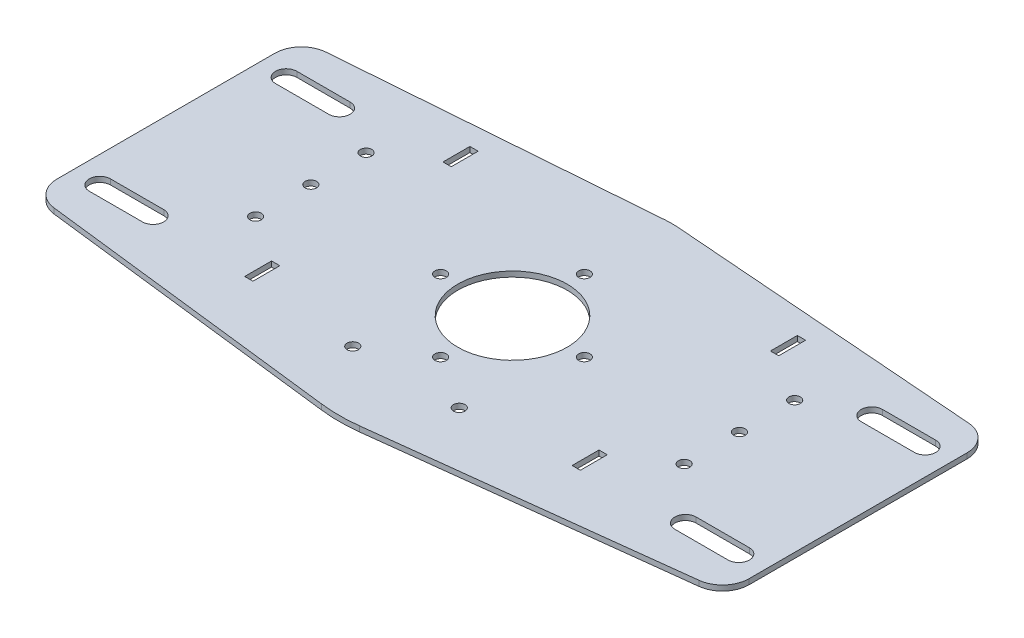
SolidWorks part; units mm, degrees
note: The reader was unsure of these and kept them because the rebuilt part matched: thickness of "Base-Flange1", "Sheet-Metal8", "Sheet-Metal9".
material "AISI 316 Stainless Steel Sheet (SS)"
ref_plane "Front Plane" through (0, 0, 0) normal (0, 0, 1) x (1, 0, 0)
ref_plane "Top Plane" through (0, 0, 0) normal (0, 1, 0) x (1, 0, 0)
ref_plane "Right Plane" through (0, 0, 0) normal (1, 0, 0) x (0, 0, -1)
sketch "Sketch1" plane through (0, 0, 0) normal (0, 1, 0) x (1, 0, 0)
  line L0 (0, -44.7868) -> (0, 44.7868) construction
  line L2 (-130, -50) -> (-130, 50)
  line L3 (-130, 50) -> (130, 50) construction
  line L4 (130, -50) -> (130, 50)
  line L5 (-44.2539, 0) -> (44.2539, 0) construction
  line L8 (-130, -50) -> (-7.0677, -64.5823)
  line L9 (130, -50) -> (7.0677, -64.5823)
  line L10 (-130, 50) -> (-2.3009, 59.823)
  line L11 (-63.05, 47.05) -> (-59.95, 47.05)
  line L12 (-63.05, 47.05) -> (-63.05, 36.95)
  line L13 (-63.05, 36.95) -> (-59.95, 36.95)
  line L14 (-59.95, 47.05) -> (-59.95, 36.95)
  line L15 (-63.05, 47.05) -> (-59.95, 36.95) construction
  line L16 (-63.05, 36.95) -> (-59.95, 47.05) construction
  line L17 (-63.05, -37.55) -> (-59.95, -37.55)
  line L18 (-63.05, -37.55) -> (-63.05, -27.45)
  line L19 (-63.05, -27.45) -> (-59.95, -27.45)
  line L20 (-59.95, -37.55) -> (-59.95, -27.45)
  line L21 (-63.05, -37.55) -> (-59.95, -27.45) construction
  line L22 (-63.05, -27.45) -> (-59.95, -37.55) construction
  line L23 (2.3009, 59.823) -> (130, 50)
  line L24 (63.05, -37.55) -> (63.05, -27.45)
  line L25 (63.05, -37.55) -> (59.95, -37.55)
  line L26 (59.95, -37.55) -> (59.95, -27.45)
  line L27 (63.05, -27.45) -> (59.95, -27.45)
  line L28 (63.05, 47.05) -> (59.95, 47.05)
  line L29 (63.05, 47.05) -> (63.05, 36.95)
  line L30 (63.05, 36.95) -> (59.95, 36.95)
  line L31 (59.95, 47.05) -> (59.95, 36.95)
  line L32 (-20, -40) -> (20, -40) construction
  line L33 (-120, 35) -> (-100, 35) construction
  line L34 (-120, 39) -> (-100, 39)
  line L35 (-120, 31) -> (-100, 31)
  line L36 (120, 35) -> (100, 35) construction
  line L39 (120, 39) -> (100, 39)
  line L40 (120, 31) -> (100, 31)
  line L41 (120, -35) -> (100, -35) construction
  line L42 (120, -39) -> (100, -39)
  line L43 (120, -31) -> (100, -31)
  line L44 (-120, -35) -> (-100, -35) construction
  line L45 (-120, -39) -> (-100, -39)
  line L46 (-120, -31) -> (-100, -31)
  circle A0 centre (0, 0) radius 20.55
  circle A1 centre (0, 27) radius 1
  circle A7 centre (-80.5, 25.5) radius 1
  circle A8 centre (-80.5, 4.75) radius 1
  circle A9 centre (-80.5, -16) radius 1
  circle A10 centre (80.5, -16) radius 1
  circle A11 centre (80.5, 4.75) radius 1
  circle A12 centre (80.5, 25.5) radius 1
  arc A14 (-7.0677, -64.5823) -> (7.0677, -64.5823) centre (0, -5) ccw
  circle A17 centre (27, 0) radius 1
  circle A18 centre (0, -27) radius 1
  circle A19 centre (-27, 0) radius 1
  arc A20 (2.3009, 59.823) -> (-2.3009, 59.823) centre (0, 29.9114) ccw
  circle A21 centre (20, -40) radius 1
  circle A22 centre (-20, -40) radius 1
  arc A23 (-120, 39) -> (-120, 31) centre (-120, 35) ccw
  arc A24 (-100, 31) -> (-100, 39) centre (-100, 35) ccw
  arc A27 (120, 39) -> (120, 31) centre (120, 35) cw
  arc A28 (100, 31) -> (100, 39) centre (100, 35) cw
  arc A29 (120, -39) -> (120, -31) centre (120, -35) ccw
  arc A30 (100, -31) -> (100, -39) centre (100, -35) ccw
  arc A31 (-120, -39) -> (-120, -31) centre (-120, -35) cw
  arc A32 (-100, -31) -> (-100, -39) centre (-100, -35) cw
  point P0 (0, 0)
  point P15 (-61.5, 42)
  point P24 (0, 0)
  point P25 (0, 0)
  point P26 (0, 50)
  point P49 (-61.5, -32.5)
  point P54 (-110, 35)
  point P58 (0, 60)
  point P76 (110, 35)
  point P83 (110, -35)
  point P90 (-110, -35)
  dimension "D3" = 41.1
  dimension "D4" = 2
  dimension "D5" = 27
  dimension "D7" = 80.5
  dimension "D8" = 2
  dimension "D12" = 50
  dimension "D15" = 60
  dimension "D16" = 2
  dimension "D17" = 40
  dimension "D25" = 30
  dimension "D30" = 4
  dimension "D2" = 260
  dimension "D9" = 24.5
  dimension "D10" = 41.5
  dimension "D11" = 20.75
  dimension "D13" = 50
  dimension "D14" = 5
  dimension "D18" = 8
  dimension "D19" = 10.1
  dimension "D20" = 74.5
  dimension "D21" = 3.1
  dimension "D22" = 61.5
  dimension "D23" = 3.1
  dimension "D24" = 10.1
  dimension "D26" = 10
  dimension "D27" = 20
  dimension "D28" = 40
  dimension "D29" = 20
  dimension "D31" = 15
  dimension "D32" = 110
  dimension "D6" = 4
base flange "Base-Flange1" sketch "Sketch1" thickness 2 reverse thickness direction no parameters "D1"=4
fillet "Fillet1" radius 10 4 edges at (130, -1, 50) (-130, -1, 50) (130, -1, -50) (-130, -1, -50)
sketch "Sketch4" plane through (0, 0, 0) normal (0, 1, 0) x (1, 0, 0)
  point P0 (-27, 0)
  point P3 (0, 27)
  point P6 (27, 0)
  point P9 (0, -27)
  point P12 (20, -40)
  point P15 (-20, -40)
  point P18 (80.5, -16)
  point P21 (80.5, 25.5)
  point P24 (80.5, 4.75)
  point P27 (-80.5, 25.5)
  point P30 (-80.5, 4.75)
  point P33 (-80.5, -16)
hole_wizard "M4 Clearance Hole2" positions "Sketch4" profile "Sketch3" hole size "M4" standard "ANSI Metric"
sketch "Sketch3" plane through (-27, 0, 0) normal (1, 0, 0) x (0, 0, 1)
  line L0 (0, 0) -> (0, 137.2919)
  line L1 (0, 137.2919) -> (2.15, 136)
  line L2 (2.15, 136) -> (2.15, 0)
  line L5 (2.15, 0) -> (0, 0)
  line L10 (0, 137.2919) -> (-2.15, 136) construction
  line L11 (0, -6.35) -> (0, 107.95) construction
  dimension "Hole Dia." = 4.3
  dimension "Hole Depth" = 136
  dimension "Drill Angle" = 118
sketch "Bend-Lines1" [suppressed] plane through (0, 0, 0) normal (0, 1, 0) x (1, 0, 0)
sketch "Bounding-Box1" [suppressed] plane through (0, 0, 0) normal (0, 1, 0) x (1, 0, 0)
sheet metal parameters "Sheet-Metal8" thickness 2 parameters "D1"=4, "D7"=4
flat pattern "Flat-Pattern8" [suppressed]
sketch "Bend-Lines2" plane through (0, 0, 0) normal (0, 1, 0) x (1, 0, 0)
sketch3d "Bounding-Box2" [suppressed]
  line L0 (87.5, -45, 0) -> (-87.5, -45, 0) construction
  line L1 (87.5, 64.8047, 0) -> (-87.5, 64.8047, 0) construction
  line L2 (87.5, -45, 0) -> (87.5, 64.8047, 0) construction
  line L3 (-87.5, -45, 0) -> (-87.5, 64.8047, 0) construction
sheet metal parameters "Sheet-Metal9" thickness 2 parameters "D1"=4, "D7"=4
flat pattern "Flat-Pattern8"
sketch "Bend-Lines2" plane through (0, 0, 0) normal (0, 1, 0) x (1, 0, 0)
sketch3d "Bounding-Box2" [suppressed]
  line L0 (130, -60, 0) -> (-130, -60, 0) construction
  line L1 (130, 64.9114, 0) -> (-130, 64.9114, 0) construction
  line L2 (130, -60, 0) -> (130, 64.9114, 0) construction
  line L3 (-130, -60, 0) -> (-130, 64.9114, 0) construction
